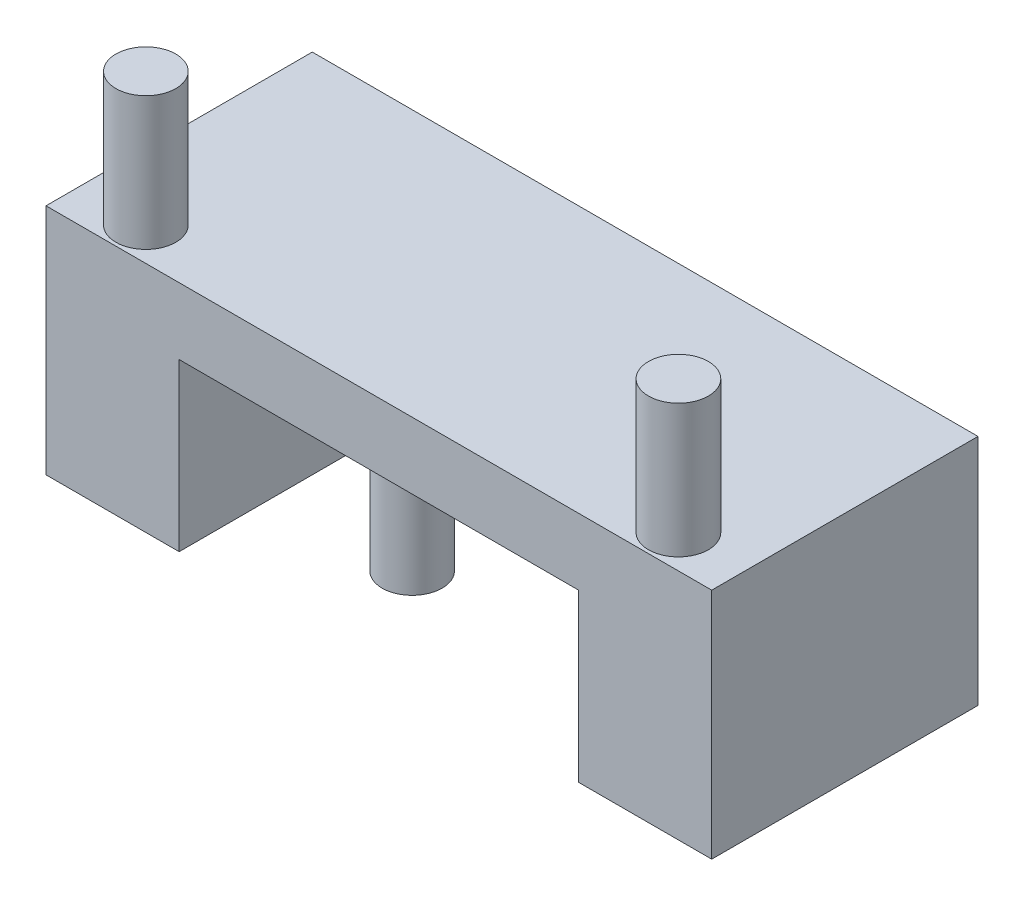
SolidWorks part; units mm, degrees
ref_plane "Front Plane" through (0, 0, 0) normal (0, 0, 1) x (1, 0, 0)
ref_plane "Top Plane" through (0, 0, 0) normal (0, 1, 0) x (1, 0, 0)
ref_plane "Right Plane" through (0, 0, 0) normal (1, 0, 0) x (0, 0, -1)
sketch "Sketch1" plane through (0, 0, 0) normal (0, 1, 0) x (1, 0, 0)
  line L1 (0, 0) -> (25.4, 0)
  line L2 (0, 0) -> (0, -10.16)
  line L3 (0, -10.16) -> (25.4, -10.16)
  line L4 (25.4, 0) -> (25.4, -10.16)
  dimension "D1" = 25.4
  dimension "D2" = 10.16
extrude "Boss-Extrude1" add sketch "Sketch1" along normal blind 8.89
ref_plane "Plane1" through (0, 6.35, 0) normal (0, 1, 0) x (1, 0, 0)
sketch "Sketch2" plane through (0, 6.35, 0) normal (0, 1, 0) x (1, 0, 0)
  line L0 (0, -10.16) -> (25.4, -10.16) construction
  line L1 (0, 0) -> (0, -10.16) construction
  line L2 (5.08, -10.16) -> (20.32, -10.16)
  line L3 (5.08, -10.16) -> (5.08, 0)
  line L4 (25.4, 0) -> (0, 0) construction
  line L5 (5.08, 0) -> (20.32, 0)
  line L6 (20.32, 0) -> (20.32, -10.16)
  line L7 (25.4, -10.16) -> (25.4, 0) construction
  dimension "D1" = 5.08
  dimension "D2" = 5.08
extrude "Cut-Extrude1" cut sketch "Sketch2" against normal blind 7.62
sketch "Sketch3" plane through (0, 8.89, 0) normal (0, 1, 0) x (1, 0, 0)
  line L0 (0, -10.16) -> (25.4, -10.16) construction
  line L1 (0, -10.16) -> (25.4, -10.16) construction
  line L4 (25.4, -10.16) -> (25.4, 0) construction
  line L5 (0, 0) -> (0, -10.16) construction
  line L6 (0, -10.16) -> (25.4, -10.16) construction
  circle A0 centre (2.54, -8.89) radius 1.143
  circle A1 centre (12.7, -8.89) radius 1.143
  circle A2 centre (22.86, -8.89) radius 1.143
  dimension "D1" = 2.286
  dimension "D2" = 2.286
  dimension "D3" = 2.286
  dimension "D4" = 1.27
  dimension "D5" = 1.27
  dimension "D6" = 2.54
  dimension "D7" = 2.54
  dimension "D8" = 1.27
extrude "Boss-Extrude2" add sketch "Sketch3" along normal blind 5.08 and the other way blind 5.08 contours A0 | A2
extrude "Boss-Extrude3" add sketch "Sketch3<5>" against normal blind 6.35 contours A1
sketch "Sketch3<5>" plane through (0, 8.89, 0) normal (0, 1, 0) x (1, 0, 0) same geometry as "Sketch3"
